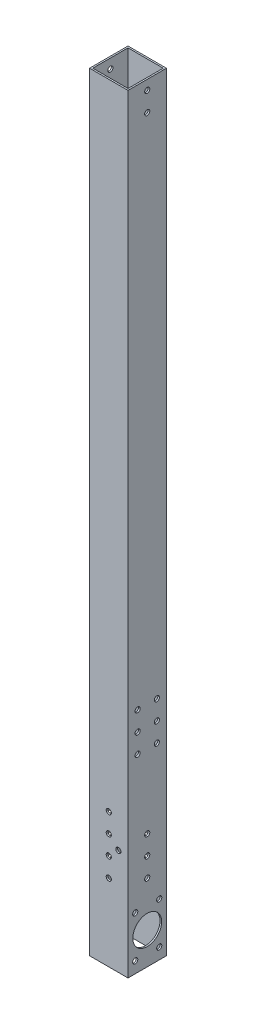
SolidWorks part; units mm, degrees
material "6061-T6 (SS)"
ref_plane "Front Plane" through (0, 0, 0) normal (0, 0, 1) x (1, 0, 0)
ref_plane "Top Plane" through (0, 0, 0) normal (0, 1, 0) x (1, 0, 0)
ref_plane "Right Plane" through (0, 0, 0) normal (1, 0, 0) x (0, 0, -1)
sketch "Sketch1" plane through (0, 0, 0) normal (0, 1, 0) x (1, 0, 0)
  line L0 (17.4625, 17.4625) -> (-17.4625, 17.4625)
  line L1 (19.05, -19.05) -> (-19.05, -19.05)
  line L2 (19.05, -19.05) -> (19.05, 19.05)
  line L3 (19.05, 19.05) -> (-19.05, 19.05)
  line L4 (-19.05, -19.05) -> (-19.05, 19.05)
  line L5 (19.05, -19.05) -> (-19.05, 19.05) construction
  line L6 (19.05, 19.05) -> (-19.05, -19.05) construction
  line L7 (-17.4625, -17.4625) -> (-17.4625, 17.4625)
  line L8 (17.4625, -17.4625) -> (-17.4625, -17.4625)
  line L9 (17.4625, -17.4625) -> (17.4625, 17.4625)
  point P0 (0, 0)
  dimension "D1" = 38.1
  dimension "D2" = 1.5875
extrude "Boss-Extrude1" add sketch "Sketch1" along normal blind 762
sketch "Sketch2" plane through (0, 0, 19.05) normal (0, 0, 1) x (1, 0, 0)
  line L1 (-19.05, 0) -> (19.05, 0) construction
  line L2 (0, 114.3) -> (9.525, 104.775) construction
  line L3 (9.525, 104.775) -> (0, 95.25) construction
  circle A0 centre (0, 76.2) radius 2.5527
  circle A1 centre (0, 95.25) radius 2.5527
  circle A4 centre (0, 114.3) radius 2.5527
  circle A5 centre (0, 133.35) radius 2.5527
  circle A7 centre (9.525, 104.775) radius 2.5527
  point P16 (0, 0)
  dimension "D4" = 19.05
  dimension "D5" = 76.2
  dimension "D6" = 19.05
  dimension "D7" = 19.05
  dimension "D8" = 9.525
extrude "Cut-Extrude1" cut sketch "Sketch2" against normal through all
sketch "Sketch3" plane through (19.05, 0, 0) normal (1, 0, 0) x (0, 0, -1)
  line L0 (-19.05, 0) -> (19.05, 0) construction
  line L1 (9.525, 206.375) -> (19.05, 206.375) construction
  line L2 (19.05, 762) -> (19.05, 0) construction
  line L3 (-9.525, 206.375) -> (-19.05, 206.375) construction
  line L4 (-19.05, 762) -> (-19.05, 0) construction
  line L5 (-19.05, 762) -> (19.05, 762) construction
  circle A0 centre (0, 76.2) radius 2.5527
  circle A1 centre (0, 95.25) radius 2.5527
  circle A2 centre (0, 114.3) radius 2.5527
  circle A3 centre (-9.525, 225.425) radius 2.5527
  circle A4 centre (-9.525, 206.375) radius 2.5527
  circle A5 centre (-9.525, 187.325) radius 2.5527
  circle A6 centre (9.525, 187.325) radius 2.5527
  circle A7 centre (9.525, 206.375) radius 2.5527
  circle A8 centre (9.525, 225.425) radius 2.5527
  circle A9 centre (0, 752.475) radius 2.5527
  circle A10 centre (0, 733.425) radius 2.5527
  point P10 (0, 0)
  dimension "D1" = 19.05
  dimension "D2" = 19.05
  dimension "D3" = 19.05
  dimension "D4" = 5.1054
  dimension "D5" = 5.1054
  dimension "D7" = 19.05
  dimension "D8" = 19.05
  dimension "D10" = 9.525
  dimension "D6" = 19.05
  dimension "D9" = 206.375
extrude "Cut-Extrude2" cut sketch "Sketch3" against normal through all
sketch "Sketch4" plane through (19.05, 0, 0) normal (1, 0, 0) x (0, 0, -1)
  line L0 (-19.05, 0) -> (19.05, 0) construction
  circle A0 centre (0, 31.75) radius 14.2875
  circle A1 centre (-11.9063, 52.3722) radius 2.5527
  circle A2 centre (11.9063, 52.3722) radius 2.5527
  circle A3 centre (11.9063, 11.1278) radius 2.5527
  circle A4 centre (-11.9063, 11.1278) radius 2.5527
  circle A5 centre (0, 31.75) radius 23.8125 construction
  point P16 (0, 0)
  dimension "D1" = 5.1054
  dimension "D2" = 47.625
  dimension "D3" = 60
  dimension "D4" = 31.75
  dimension "D5" = 28.575
extrude "Cut-Extrude3" cut sketch "Sketch4" against normal through all
